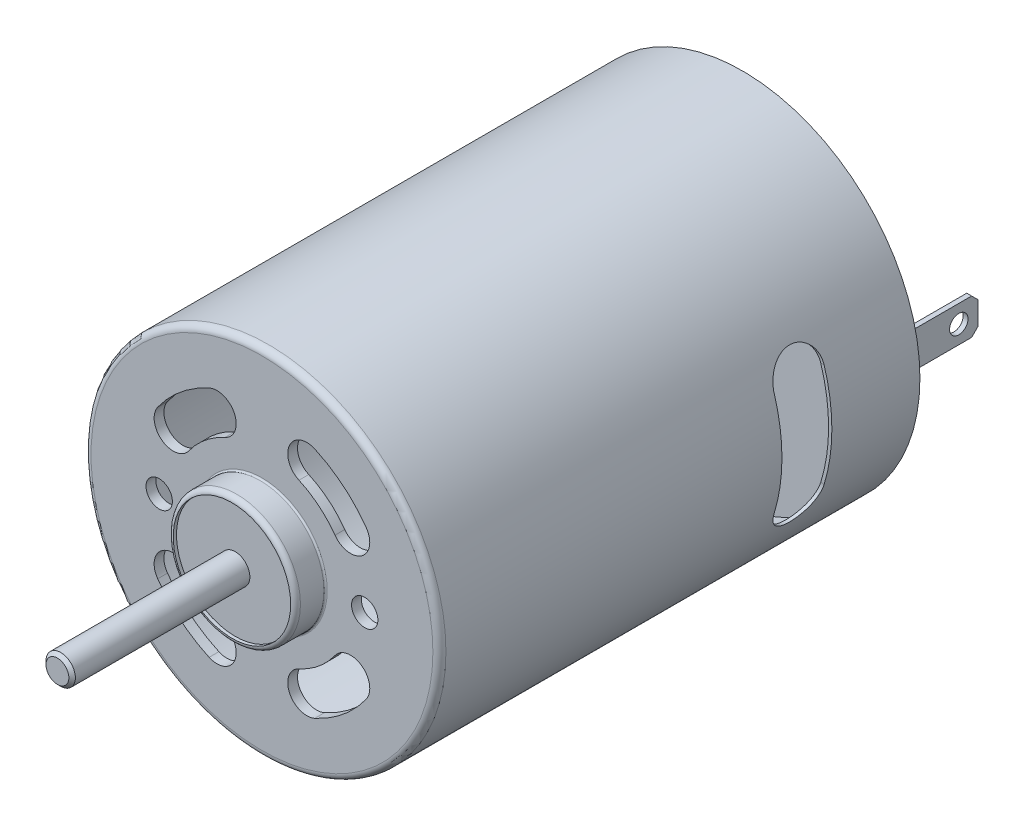
SolidWorks part; units mm, degrees
material "PW110:Mi:0:244:Ar:0:-1:C1:1:2:3:Re:27:Di:35:"
ref_plane "Front" through (0, 0, 0) normal (0, 0, 1) x (1, 0, 0)
ref_plane "Top" through (0, 0, 0) normal (0, 1, 0) x (1, 0, 0)
ref_plane "Right" through (0, 0, 0) normal (1, 0, 0) x (0, 0, -1)
sketch "Sketch1" plane through (0, 0, 0) normal (0, 0, 1) x (1, 0, 0)
  circle A0 centre (0, 0) radius 13.8176
  dimension "D1" = 27.6352
extrude "Extrude1" add sketch "Sketch1" against normal blind 37.4142
fillet "Fillet1" radius 0.508 1 edges at (13.8176, 0, 0)
sketch "Sketch2" plane through (0, 0, 0) normal (0, 0, 1) x (1, 0, 0)
  circle A0 centre (0, 0) radius 4.953
  dimension "D1" = 9.906
extrude "Extrude2" add sketch "Sketch2" along normal blind 2.3368
fillet "Fillet2" radius 0.381 1 edges at (4.953, 0, 2.3368)
sketch "Sketch3" plane through (0, 0, 2.3368) normal (0, 0, 1) x (1, 0, 0)
  circle A0 centre (0, 0) radius 1.143
  dimension "D1" = 2.286
extrude "Extrude3" add sketch "Sketch3" along normal blind 13.589
chamfer "Chamfer1" distance 0.254 angle 45 1 edges at (1.143, 0, 15.9258)
hole_wizard "M2.5x0.45 Tapped Hole1" positions "Sketch5" profile "Sketch4" tap size "M2.5x0.45" standard "Ansi Metric"
sketch "Sketch5" plane through (0, 0, 0) normal (0, 0, 1) x (1, 0, 0)
  point P0 (-8.001, 0)
  point P1 (8.001, 0)
  dimension "D1" = 8.001
  dimension "D2" = 16.002
sketch "Sketch4" plane through (-8.001, 0, 0) normal (1, 0, 0) x (0, -1, 0)
  line L0 (0, 0) -> (0, 3.1559)
  line L1 (0, 3.1559) -> (1.025, 2.54)
  line L2 (1.025, 2.54) -> (1.025, 0)
  line L5 (1.025, 0) -> (0, 0)
  line L10 (0, 3.1559) -> (-1.025, 2.54) construction
  line L11 (0, -6.35) -> (0, 107.95) construction
  dimension "Tap Drill Dia." = 2.05
  dimension "Tap Drill Depth" = 2.54
  dimension "Drill Angle" = 118
cosmetic thread "Cosmetic Thread1" parameters "D1"=0.762, "D2"=2.5
cosmetic thread "Cosmetic Thread2" parameters "D1"=0.762, "D2"=2.5
sketch "Sketch6" plane through (0, 0, 0) normal (0, 0, 1) x (1, 0, 0)
  line L0 (0, 0) -> (0, 15.307) construction
  line L1 (2.0066, -0.216) -> (2.0066, 15.091) construction
  line L2 (0, 0) -> (16.256, 0) construction
  line L3 (-0.8636, 3.429) -> (15.3924, 3.429) construction
  arc A0 (5.6875, 4.055) -> (2.8829, 6.3623) centre (0, 0) ccw
  arc A1 (8.1176, 5.7875) -> (4.1148, 9.0807) centre (0, 0) ccw
  arc A2 (4.1148, 9.0807) -> (2.8829, 6.3623) centre (3.4989, 7.7215) ccw
  arc A3 (5.6875, 4.055) -> (8.1176, 5.7875) centre (6.9025, 4.9213) ccw
  arc A4 (-5.6875, 4.055) -> (-8.1176, 5.7875) centre (-6.9025, 4.9212) cw
  arc A5 (-5.6875, 4.055) -> (-2.8829, 6.3623) centre (0, 0) cw
  arc A6 (-4.1148, 9.0807) -> (-2.8829, 6.3623) centre (-3.4989, 7.7215) cw
  arc A7 (-8.1176, 5.7875) -> (-4.1148, 9.0807) centre (0, 0) cw
  arc A8 (-5.6875, -4.055) -> (-8.1176, -5.7875) centre (-6.9025, -4.9212) ccw
  arc A9 (-8.1176, -5.7875) -> (-4.1148, -9.0807) centre (0, 0) ccw
  arc A10 (-5.6875, -4.055) -> (-2.8829, -6.3623) centre (0, 0) ccw
  arc A11 (-4.1148, -9.0807) -> (-2.8829, -6.3623) centre (-3.4989, -7.7215) ccw
  arc A12 (4.1148, -9.0807) -> (2.8829, -6.3623) centre (3.4989, -7.7215) cw
  arc A13 (5.6875, -4.055) -> (2.8829, -6.3623) centre (0, 0) cw
  arc A14 (5.6875, -4.055) -> (8.1176, -5.7875) centre (6.9025, -4.9213) cw
  arc A15 (8.1176, -5.7875) -> (4.1148, -9.0807) centre (0, 0) cw
  dimension "D1" = 13.97
  dimension "D2" = 19.939
  dimension "D3" = 2.0066
  dimension "D4" = 3.429
extrude "Cut-Extrude1" cut sketch "Sketch6" against normal blind 2.54
ref_plane "Plane1" through (0, 0, -0.762) normal (0, 0, 1) x (1, 0, 0)
sketch "Sketch7" plane through (0, 0, -0.762) normal (0, 0, 1) x (1, 0, 0)
  circle A4 centre (0, 0) radius 13.5636
  circle A5 centre (0, 0) radius 13.5636
  dimension "D1" = 0.254
extrude "Cut-Extrude2" cut sketch "Sketch7" against normal blind 34.3272
sketch "Sketch8" plane through (0, 0, 0) normal (1, 0, 0) x (0, 0, -1)
  line L0 (26.67, 4.0259) -> (26.67, -4.0259)
  line L1 (30.5562, -4.0259) -> (30.5562, 4.0259)
  line L2 (0, 13.3096) -> (0, -13.3096) construction
  line L3 (-3.867, 0) -> (39.0991, 0) construction
  line L4 (-3.867, -5.969) -> (39.0991, -5.969) construction
  arc A0 (26.67, -4.0259) -> (30.5562, -4.0259) centre (28.6131, -4.0259) ccw
  arc A1 (26.67, 4.0259) -> (30.5562, 4.0259) centre (28.6131, 4.0259) cw
  dimension "D1" = 3.8862
  dimension "D2" = 26.67
  dimension "D3" = 5.969
extrude "Cut-Extrude3" cut sketch "Sketch8" against normal mid plane 50.8
sketch "Sketch9" plane through (0, 0, -37.4142) normal (0, 0, -1) x (-1, 0, 0)
  circle A0 centre (0, 0) radius 4.953
  dimension "D1" = 9.906
extrude "Extrude4" add sketch "Sketch9" along normal blind 2.921
sketch "Sketch10" plane through (0, 0, -40.3352) normal (0, 0, -1) x (-1, 0, 0)
  circle A0 centre (0, 0) radius 1.143 construction
  circle A1 centre (0, 0) radius 1.143
  circle A2 centre (0, 0) radius 4.7358
extrude "Cut-Extrude4" cut sketch "Sketch10" against normal blind 0.508
sketch "Sketch11" plane through (0, 0, -37.4142) normal (0, 0, -1) x (-1, 0, 0)
  circle A1 centre (0, 0) radius 9.525
  circle A2 centre (0, 0) radius 13.5636
  circle A3 centre (0, 0) radius 13.5636
  dimension "D2" = 19.05
  dimension "D1" = 0.254
extrude "Cut-Extrude5" cut sketch "Sketch11" against normal blind 0.254
fillet "Fillet3" radius 0.127 4 edges at (-9.525, 0, -37.1602) (-9.525, 0, -37.4142) (4.953, 0, -37.4142) (4.953, 0, 0)
sketch "Sketch12" plane through (0, 0, -37.1602) normal (0, 0, -1) x (-1, 0, 0)
  line L1 (11.303, 1.397) -> (11.684, 1.397)
  line L2 (11.303, 1.397) -> (11.303, -1.397)
  line L3 (11.303, -1.397) -> (11.684, -1.397)
  line L4 (11.684, 1.397) -> (11.684, -1.397)
  dimension "D1" = 0.381
  dimension "D2" = 2.794
  dimension "D3" = 1.397
  dimension "D4" = 11.684
extrude "Extrude5" add sketch "Sketch12" along normal blind 6.9088
mirror "Mirror1" about plane through (0, 0, 0) normal (1, 0, 0) of "Extrude5"
chamfer "Chamfer2" distance 0.4953 angle 45 4 edges at (11.4935, 1.397, -44.069) (11.4935, -1.397, -44.069) (-11.4935, 1.397, -44.069) (-11.4935, -1.397, -44.069)
sketch "Sketch13" plane through (0, 0, 0) normal (1, 0, 0) x (0, 0, -1)
  circle A0 centre (42.5745, 0) radius 0.719
extrude "Cut-Extrude6" cut sketch "Sketch13" against normal mid plane 50.8
sketch "Sketch14" plane through (0, 0, -37.1602) normal (0, 0, -1) x (-1, 0, 0)
  line L8 (11.938, -1.651) -> (11.938, 1.651)
  line L9 (11.049, -1.651) -> (11.938, -1.651)
  line L10 (11.049, 1.651) -> (11.049, -1.651)
  line L11 (11.938, 1.651) -> (11.049, 1.651)
  line L12 (11.938, -1.524) -> (11.938, 1.524)
  line L13 (11.176, -1.651) -> (11.811, -1.651)
  line L14 (11.049, 1.524) -> (11.049, -1.524)
  line L15 (11.811, 1.651) -> (11.176, 1.651)
  line L20 (11.2522, -1.4478) -> (11.7348, -1.4478)
  line L21 (11.2522, 1.4478) -> (11.2522, -1.4478)
  line L22 (11.7348, 1.4478) -> (11.2522, 1.4478)
  line L23 (11.7348, -1.4478) -> (11.7348, 1.4478)
  line L24 (11.2522, -1.4478) -> (11.7348, -1.4478)
  line L25 (11.2522, 1.4478) -> (11.2522, -1.4478)
  line L26 (11.7348, 1.4478) -> (11.2522, 1.4478)
  line L27 (11.7348, -1.4478) -> (11.7348, 1.4478)
  arc A0 (11.811, 1.651) -> (11.938, 1.524) centre (11.811, 1.524) cw
  arc A1 (11.049, 1.524) -> (11.176, 1.651) centre (11.176, 1.524) cw
  arc A2 (11.176, -1.651) -> (11.049, -1.524) centre (11.176, -1.524) cw
  arc A3 (11.938, -1.524) -> (11.811, -1.651) centre (11.811, -1.524) cw
  dimension "D2" = 0.127
  dimension "D1" = 0.254
  dimension "D3" = 0.0508
extrude "Extrude6" add sketch "Sketch14" along normal blind 0.635 draft 2
fillet "Fillet5" radius 0.0508 12 edges at (-11.4935, -1.47, -37.7952) (-11.757, 0, -37.7952) (-11.4935, 1.47, -37.7952) (-11.23, 0, -37.7952) (-11.9158, 0, -37.7952) (-11.8851, -1.5981, -37.7952) (-11.4935, -1.6288, -37.7952) (-11.1019, -1.5981, -37.7952) (-11.0712, 0, -37.7952) (-11.1019, 1.5981, -37.7952) (-11.4935, 1.6288, -37.7952) (-11.8851, 1.5981, -37.7952)
mirror "Mirror2" about plane through (0, 0, 0) normal (1, 0, 0) of "Fillet5", "Extrude6"
chamfer "Chamfer3" distance 0.127 angle 45 1 edges at (-1.143, 0, -40.3352)
sketch "Sketch15" plane through (0, 0, 2.3368) normal (0, 0, 1) x (1, 0, 0)
  circle A0 centre (0, 0) radius 1.143 construction
  circle A1 centre (0, 0) radius 4.572
  circle A2 centre (0, 0) radius 4.572
  circle A3 centre (0, 0) radius 1.143
  dimension "D1" = 0
extrude "Cut-Extrude7" cut sketch "Sketch15" against normal blind 0.254
scale "Scale1" scale about centroid uniform scaling yes scale factor 3
